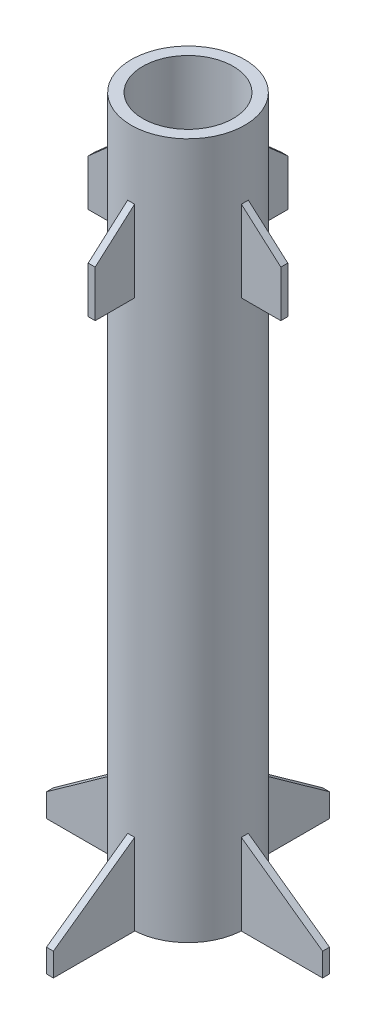
SolidWorks part; units mm, degrees
ref_plane "Plano frontal" through (0, 0, 0) normal (0, 0, 1) x (1, 0, 0)
ref_plane "Plano superior" through (0, 0, 0) normal (0, 1, 0) x (1, 0, 0)
ref_plane "Plano direito" through (0, 0, 0) normal (1, 0, 0) x (0, 0, -1)
sketch "Esboço1" plane through (0, 0, 0) normal (0, 1, 0) x (1, 0, 0)
  circle A0 centre (0, 0) radius 19.5
  circle A1 centre (0, 0) radius 24.5
  dimension "D1" = 39
  dimension "D2" = 49
extrude "Ressalto-extrusão1" add sketch "Esboço1" along normal blind 300
sketch "Esboço2" plane through (0, 0, 0) normal (0, 0, 1) x (1, 0, 0)
  line L0 (24.5, 0) -> (59.5, 0)
  line L1 (59.5, 0) -> (59.5, 10)
  line L2 (59.5, 10) -> (24.5, 35)
  line L3 (24.5, 0) -> (24.5, 300) construction
  line L6 (24.5, 271.3029) -> (24.5, 236.3029)
  line L7 (24.5, 35) -> (24.5, 0)
  line L8 (24.5, 271.3029) -> (41.5, 256.3029)
  line L9 (41.5, 256.3029) -> (41.5, 236.3029)
  line L11 (24.5, 236.3029) -> (41.5, 236.3029)
  dimension "D1" = 17
  dimension "D2" = 35
  dimension "D3" = 35
  dimension "D4" = 35
  dimension "D5" = 20
  dimension "D6" = 10
extrude "Ressalto-extrusão2" add sketch "Esboço2" along normal mid plane 3 separate body contours L9 L11 L6 L8
extrude "Ressalto-extrusão3" add sketch "Esboço2<3>" along normal mid plane 3
sketch "Esboço2<3>" plane through (0, 0, 0) normal (0, 0, 1) x (1, 0, 0) same geometry as "Esboço2"
pattern_circular "PadrãoCircular17" count 4 over 360 about axis through (0, 300, 0) along (0, -1, 0) of bodies 106
pattern_circular "PadrãoCircular18" count 4 over 360 about axis through (0, 300, 0) along (0, -1, 0) reverse direction yes of bodies 107
sketch "Esboço3" plane through (-1.5, 0, 0) normal (-1, 0, 0) x (0, 0, 1)
